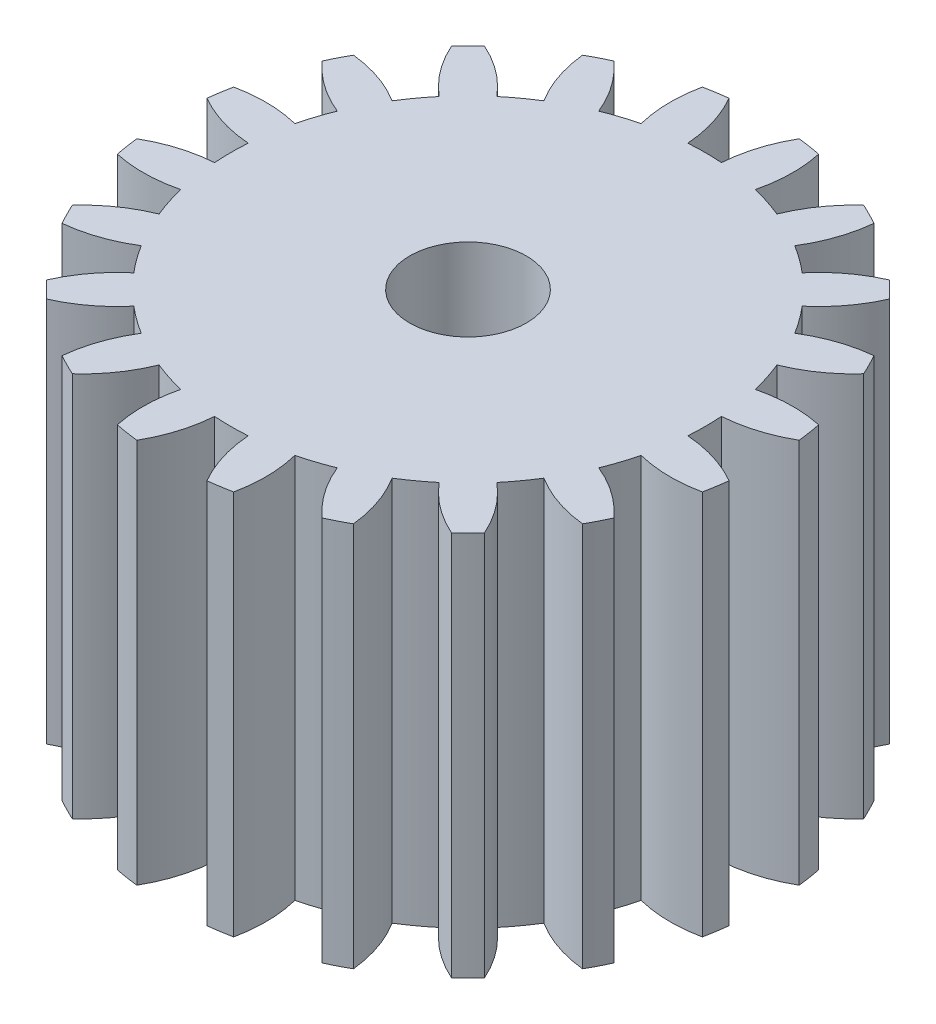
SolidWorks part; units mm, degrees
ref_plane "Front Plane" through (0, 0, 0) normal (0, 0, 1) x (1, 0, 0)
ref_plane "Top Plane" through (0, 0, 0) normal (0, 1, 0) x (1, 0, 0)
ref_plane "Right Plane" through (0, 0, 0) normal (1, 0, 0) x (0, 0, -1)
sketch "Sketch1" plane through (0, 0, 0) normal (0, 1, 0) x (1, 0, 0)
  circle A0 centre (0, 0) radius 8.255
  dimension "D1" = 16.51
extrude "Boss-Extrude1" add sketch "Sketch1" along normal blind 10.668 contours A0
sketch "Sketch2" plane through (0, 10.668, 0) normal (0, 1, 0) x (1, 0, 0)
  circle A0 centre (0, 0) radius 1.6129
  dimension "D1" = 3.2258
extrude "Cut-Extrude1" cut sketch "Sketch2" against normal through all
sketch "Sketch3" plane through (0, 10.668, 0) normal (0, 1, 0) x (1, 0, 0)
  line L1 (0, 0) -> (0, 12.3699) construction
  line L3 (1.4263, 8.8274) -> (-1.4263, 8.8274)
  arc A1 (0.4655, 6.5494) -> (-0.4655, 6.5494) centre (0, 0) ccw
  arc A3 (0.4655, 6.5494) -> (1.4263, 8.8274) centre (4.2908, 6.2775) cw
  arc A4 (-0.4655, 6.5494) -> (-1.4263, 8.8274) centre (-4.2908, 6.2775) ccw
  point P7 (-0.7625, 8.3198)
  point P9 (0.7625, 8.3198)
  point P13 (0, 8.8274)
extrude "Cut-Extrude6" cut sketch "Sketch3" against normal through all contours A1 A4 L3 A3
pattern_circular "CirPattern1" count 20 over 360 about axis through (0, 10.668, 0) along (0, 1, 0) of "Cut-Extrude6"
